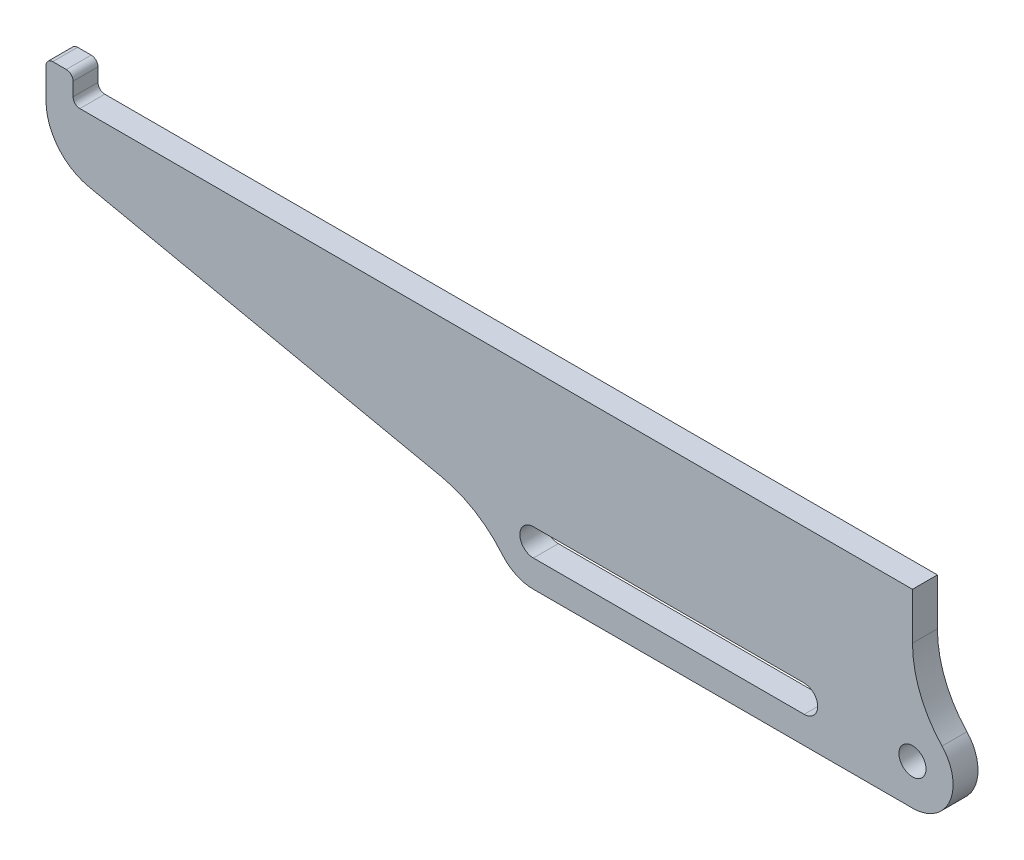
SolidWorks part; units mm, degrees
ref_plane "Front Plane" through (0, 0, 0) normal (0, 0, 1) x (1, 0, 0)
ref_plane "Top Plane" through (0, 0, 0) normal (0, 1, 0) x (1, 0, 0)
ref_plane "Right Plane" through (0, 0, 0) normal (1, 0, 0) x (0, 0, -1)
sketch "Sketch1" plane through (0, 0, 0) normal (0, 0, 1) x (1, 0, 0)
  line L0 (44.45, 0) -> (-44.45, 0) construction
  line L1 (44.45, -9.525) -> (-44.45, -9.525)
  line L3 (44.45, 0) -> (-44.45, 0) construction
  line L4 (19.05, -3.175) -> (-44.45, -3.175)
  line L5 (19.05, 3.175) -> (-44.45, 3.175)
  line L6 (-158.75, 22.225) -> (-53.975, 0)
  line L8 (44.45, 9.525) -> (44.45, 34.925)
  line L9 (44.45, 34.925) -> (-158.75, 34.925)
  line L10 (-158.75, 22.225) -> (-158.75, 34.925)
  line L11 (44.45, 9.525) -> (-158.75, 34.925) construction
  line L12 (44.45, 34.925) -> (-158.75, 9.525) construction
  arc A0 (44.45, -9.525) -> (44.45, 9.525) centre (44.45, 0) ccw
  arc A1 (-53.975, 0) -> (-44.45, -9.525) centre (-44.45, 0) ccw
  circle A2 centre (44.45, 0) radius 3.175
  arc A3 (-44.45, 3.175) -> (-44.45, -3.175) centre (-44.45, 0) ccw
  arc A4 (19.05, -3.175) -> (19.05, 3.175) centre (19.05, 0) ccw
  point P2 (0, 0)
  point P10 (0, 0)
  point P19 (-57.15, 22.225)
  dimension "D2" = 9.525
  dimension "D1" = 88.9
  dimension "D4" = 203.2
  dimension "D5" = 25.4
  dimension "D6" = 63.5
extrude "Boss-Extrude1" add sketch "Sketch1" along normal blind 5.842
fillet "Fillet1" radius 25.4 1 edges at (44.45, 9.525, 2.921)
fillet "Fillet2" radius 25.4 1 edges at (-53.975, 0, 2.921)
fillet "Fillet3" radius 12.7 1 edges at (-158.75, 22.225, 2.921)
sketch "Sketch2" plane through (0, 0, 5.842) normal (0, 0, 1) x (1, 0, 0)
  line L0 (-158.75, 34.925) -> (-158.75, 41.275)
  line L1 (-158.75, 41.275) -> (-152.4, 41.275)
  line L2 (-152.4, 41.275) -> (-152.4, 34.925)
  line L3 (44.45, 34.925) -> (-158.75, 34.925) construction
  line L4 (-152.4, 34.925) -> (-158.75, 34.925)
  dimension "D1" = 6.35
  dimension "D2" = 6.35
extrude "Boss-Extrude2" add sketch "Sketch2" against normal up to surface (5.842 mm away) up to face at (47.625, 0, 0)
fillet "Fillet4" radius 1.5875 3 edges at (-158.75, 41.275, 2.921) (-152.4, 41.275, 2.921)
